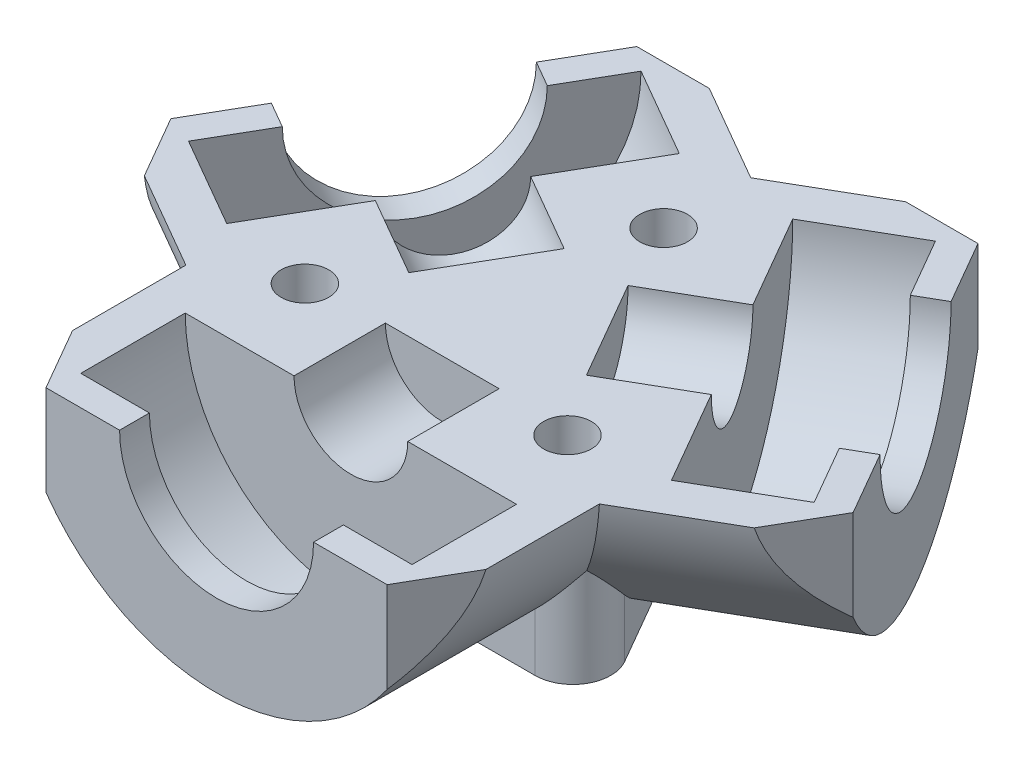
SolidWorks part; units mm, degrees
ref_plane "Front Plane" through (0, 0, 0) normal (0, 0, 1) x (1, 0, 0)
ref_plane "Top Plane" through (0, 0, 0) normal (0, 1, 0) x (1, 0, 0)
ref_plane "Right Plane" through (0, 0, 0) normal (1, 0, 0) x (0, 0, -1)
sketch "Sketch1" plane through (0, 0, 0) normal (0, 1, 0) x (1, 0, 0)
  line L1 (11.43, -19.7973) -> (22.86, 0)
  line L2 (22.86, 0) -> (11.43, 19.7973)
  line L3 (11.43, 19.7973) -> (-11.43, 19.7973)
  line L4 (-11.43, 19.7973) -> (-22.86, 0)
  line L5 (-22.86, 0) -> (-11.43, -19.7973)
  line L6 (-11.43, -19.7973) -> (11.43, -19.7973)
  circle A0 centre (0, 0) radius 19.7973 construction
  dimension "D1" = 22.86
extrude "Boss-Extrude1" add sketch "Sketch1" along normal blind 12.7 contours L4 L5 L6 L1 L2 L3
sketch "Sketch5" plane through (0, 12.7, 0) normal (0, 1, 0) x (1, 0, 0)
  line L14 (0, -19.7973) -> (0, -4.6723)
  line L15 (-11.43, -19.7973) -> (11.43, -19.7973) construction
  line L16 (0, -4.6723) -> (-3.81, -4.6723)
  line L17 (-3.81, -4.6723) -> (-3.81, -10.7973)
  line L18 (-3.81, -10.7973) -> (-11.1, -10.7973)
  line L19 (-11.1, -10.7973) -> (-11.1, -17.7973)
  line L20 (-11.1, -17.7973) -> (-6.5, -17.7973)
  line L21 (-6.5, -17.7973) -> (-6.5, -19.7973)
  line L22 (-6.5, -19.7973) -> (0, -19.7973)
  dimension "D1" = 6.5
  dimension "D2" = 11.1
  dimension "D3" = 2
  dimension "D4" = 7
  dimension "D5" = 6.125
  dimension "D6" = 3.81
revolve "Cut-Revolve1" cut sketch "Sketch5" angle 360 about L14
sketch "Sketch7" plane through (0, 12.7, 0) normal (0, 1, 0) x (1, 0, 0)
  circle A0 centre (0, 10.16) radius 1.6
  circle A1 centre (8.7988, -5.08) radius 1.6
  circle A2 centre (-8.7988, -5.08) radius 1.6
  circle A3 centre (0, 0) radius 10.16 construction
  point P6 (0, 0)
  point P7 (9.8675, -8.3626)
  point P11 (0, 0)
  point P12 (0, 0)
  dimension "D1" = 3.2
  dimension "D2" = 20.32
  dimension "D3" = 3
extrude "Cut-Extrude2" cut sketch "Sketch7" against normal up to surface (12.7 mm away) up to face at (0, 0, 0)
ref_axis "Axis1" through (0, -0.635, 0) along (0, 1, 0)
pattern_circular "CirPattern1" count 3 over 360 about axis through (0, -0.635, 0) along (0, 1, 0) of "Cut-Revolve1"
sketch "Sketch8" plane through (0, 0, 19.7973) normal (0, 0, 1) x (1, 0, 0)
  line L0 (-3.81, 12.7) -> (3.81, 12.7) construction
  line L1 (-13.8564, 12.7) -> (-18.6629, 12.7)
  line L2 (-22.86, 12.7) -> (-11.43, 12.7) construction
  line L3 (-18.6629, 12.7) -> (-18.6629, 0)
  line L4 (-22.86, 0) -> (-11.43, 0) construction
  line L5 (-18.6629, 0) -> (18.6629, 0)
  line L6 (11.43, 0) -> (22.86, 0) construction
  line L7 (18.6629, 0) -> (18.6629, 12.7)
  line L8 (11.43, 12.7) -> (22.86, 12.7) construction
  line L9 (18.6629, 12.7) -> (13.8564, 12.7)
  arc A0 (-13.8564, 12.7) -> (13.8564, 12.7) centre (0, 14.7) ccw
  dimension "D1" = 14
  dimension "D2" = 2
extrude "Cut-Extrude3" cut sketch "Sketch8" against normal blind 11.684
pattern_circular "CirPattern2" count 3 over 360 about axis through (0, -0.635, 0) along (0, 1, 0) of "Cut-Extrude3"
sketch "Sketch10" plane through (0, 0, 0) normal (0, -1, 0) x (1, 0, 0)
  line L3 (14.0527, 8.1133) -> (-14.0527, 8.1133)
  line L4 (-14.0527, 8.1133) -> (0, -16.2267)
  line L5 (0, -16.2267) -> (14.0527, 8.1133)
  line L6 (14.0527, 8.1133) -> (-14.0527, 8.1133)
  line L7 (-14.0527, 8.1133) -> (0, -16.2267)
  line L8 (0, -16.2267) -> (14.0527, 8.1133)
  dimension "D1" = 0
extrude "Cut-Extrude5" cut sketch "Sketch10" against normal blind 0.7
fillet "Fillet2" radius 2.54 3 edges at (14.0527, 6.7, 8.1133) (0, 6.7, -16.2267) (-14.0527, 6.7, 8.1133)
